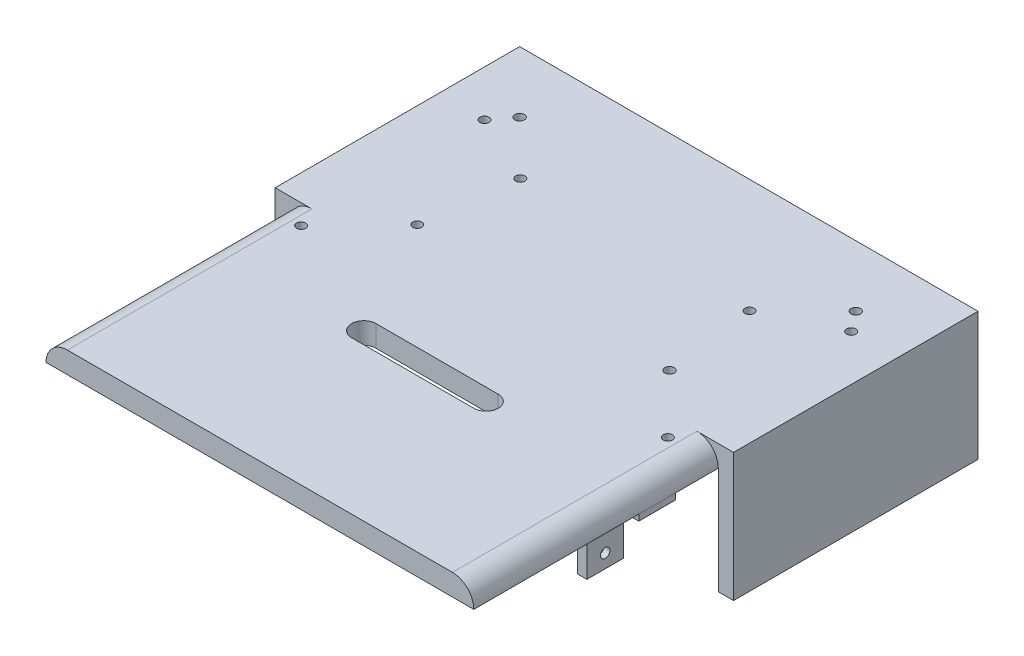
SolidWorks part; units mm, degrees
ref_plane "Front Plane" through (0, 0, 0) normal (0, 0, 1) x (1, 0, 0)
ref_plane "Top Plane" through (0, 0, 0) normal (0, 1, 0) x (1, 0, 0)
ref_plane "Right Plane" through (0, 0, 0) normal (1, 0, 0) x (0, 0, -1)
sketch "Sketch1" plane through (0, 0, 0) normal (0, 0, 1) x (1, 0, 0)
  line L0 (-95.0617, -14.5514) -> (-95.0617, 27.4486)
  line L1 (-95.0617, 27.4486) -> (54.9383, 27.4486)
  line L2 (54.9383, 27.4486) -> (54.9383, -14.5514)
  line L3 (54.9383, -14.5514) -> (49.9383, -14.5514)
  line L4 (49.9383, -14.5514) -> (49.9383, 20.4486)
  line L5 (49.9383, 20.4486) -> (-90.0617, 20.4486)
  line L6 (-90.0617, 20.4486) -> (-90.0617, -14.5514)
  line L7 (-90.0617, -14.5514) -> (-95.0617, -14.5514)
  dimension "D1" = 150
  dimension "D2" = 5
  dimension "D3" = 5
  dimension "D4" = 42
  dimension "D5" = 42
  dimension "D6" = 35
  dimension "D7" = 35
  dimension "D8" = 7
extrude "Boss-Extrude1" add sketch "Sketch1" along normal blind 160
sketch "Sketch2" plane through (0, 0, 0) normal (0, 0, -1) x (-1, 0, 0)
  line L0 (-52.4383, 15.4486) -> (-52.4383, -4.5514) construction
  line L1 (-50.9383, 15.4486) -> (-50.9383, -4.5514)
  line L2 (-53.9383, 15.4486) -> (-53.9383, -4.5514)
  line L3 (-4.9383, 23.9486) -> (45.0617, 23.9486) construction
  line L4 (-4.9383, 25.4486) -> (45.0617, 25.4486)
  line L5 (-4.9383, 22.4486) -> (45.0617, 22.4486)
  line L6 (92.5617, 15.4486) -> (92.5617, -4.5514) construction
  line L7 (94.0617, 15.4486) -> (94.0617, -4.5514)
  line L8 (91.0617, 15.4486) -> (91.0617, -4.5514)
  line L9 (-54.9383, 27.4486) -> (95.0617, 27.4486) construction
  line L12 (90.0617, 20.4486) -> (-49.9383, 20.4486) construction
  line L13 (-54.9383, -14.5514) -> (-54.9383, 27.4486) construction
  line L14 (-49.9383, 20.4486) -> (-49.9383, -14.5514) construction
  line L15 (90.0617, -14.5514) -> (90.0617, 20.4486) construction
  arc A0 (-50.9383, 15.4486) -> (-53.9383, 15.4486) centre (-52.4383, 15.4486) ccw
  arc A1 (-53.9383, -4.5514) -> (-50.9383, -4.5514) centre (-52.4383, -4.5514) ccw
  arc A2 (-4.9383, 25.4486) -> (-4.9383, 22.4486) centre (-4.9383, 23.9486) ccw
  arc A3 (45.0617, 22.4486) -> (45.0617, 25.4486) centre (45.0617, 23.9486) ccw
  arc A4 (94.0617, 15.4486) -> (91.0617, 15.4486) centre (92.5617, 15.4486) ccw
  arc A5 (91.0617, -4.5514) -> (94.0617, -4.5514) centre (92.5617, -4.5514) ccw
  point P2 (-52.4383, 5.4486)
  point P7 (20.0617, 23.9486)
  point P14 (92.5617, 5.4486)
  dimension "D1" = 22
  dimension "D2" = 3
  dimension "D3" = 20
  dimension "D4" = 2.5
  dimension "D5" = 3
  dimension "D6" = 20
  dimension "D7" = 2.5
  dimension "D8" = 22
  dimension "D9" = 3.5
  dimension "D10" = 3
  dimension "D11" = 50
  dimension "D12" = 75
extrude "Cut-Extrude1" cut sketch "Sketch2" against normal blind 32
sketch "Sketch3" plane through (-95.0617, 0, 0) normal (-1, 0, 0) x (0, 0, 1)
  line L0 (0, 27.4486) -> (0, -14.5514) construction
  line L3 (160, 27.4486) -> (0, 27.4486) construction
  circle A0 centre (120, 7.4486) radius 7.5
  dimension "D1" = 15
  dimension "D3" = 20
  dimension "D2" = 120
extrude "Cut-Extrude2" cut sketch "Sketch3" against normal blind 210
sketch "Sketch5" plane through (0, 27.4486, 0) normal (0, 1, 0) x (1, 0, 0)
  line L0 (54.9383, 0) -> (-95.0617, 0) construction
  line L1 (-95.0617, -160) -> (-95.0617, 0) construction
  line L2 (54.9383, -160) -> (54.9383, 0) construction
  circle A0 centre (-80.0617, -26.5) radius 1.5
  circle A1 centre (39.9383, -26.5) radius 1.5
  circle A2 centre (-80.0617, -86.5) radius 1.5
  circle A3 centre (39.9383, -86.5) radius 1.5
  dimension "D1" = 3
  dimension "D2" = 3
  dimension "D7" = 3
  dimension "D8" = 3
  dimension "D3" = 26.5
  dimension "D4" = 15
  dimension "D5" = 15
  dimension "D6" = 26.5
  dimension "D9" = 60
  dimension "D10" = 60
  dimension "D11" = 15
  dimension "D12" = 15
extrude "Cut-Extrude4" cut sketch "Sketch5" against normal blind 210
sketch "Sketch7" plane through (0, 27.4486, 0) normal (0, 1, 0) x (1, 0, 0)
  line L0 (-40.0617, -106) -> (-0.0617, -106) construction
  line L1 (-40.0617, -102) -> (-0.0617, -102)
  line L2 (-40.0617, -110) -> (-0.0617, -110)
  line L3 (-95.0617, -160) -> (-95.0617, 0) construction
  line L4 (54.9383, -160) -> (-95.0617, -160) construction
  arc A0 (-40.0617, -102) -> (-40.0617, -110) centre (-40.0617, -106) ccw
  arc A1 (-0.0617, -110) -> (-0.0617, -102) centre (-0.0617, -106) ccw
  point P2 (-20.0617, -106)
  dimension "D1" = 40
  dimension "D2" = 75
  dimension "D3" = 8
  dimension "D4" = 50
extrude "Cut-Extrude6" cut sketch "Sketch7" against normal blind 20
ref_plane "Plane5" through (-20.0617, 0, 0) normal (-1, 0, 0) x (0, 0, 1)
sketch "Sketch8" plane through (0, 27.4486, 0) normal (0, 1, 0) x (1, 0, 0)
  line L0 (54.9383, 0) -> (-95.0617, 0) construction
  line L1 (54.9383, -160) -> (54.9383, 0) construction
  line L2 (-95.0617, -160) -> (-95.0617, 0) construction
  circle A0 centre (-75.0617, -20) radius 1.55
  circle A1 centre (34.9383, -20) radius 1.55
  dimension "D1" = 3.1
  dimension "D2" = 3.1
  dimension "D3" = 20
  dimension "D4" = 20
  dimension "D5" = 20
  dimension "D6" = 20
extrude "Cut-Extrude7" cut sketch "Sketch8" against normal blind 10
sketch "Sketch9" plane through (0, 20.4486, 0) normal (0, -1, 0) x (1, 0, 0)
  line L0 (49.9383, 106) -> (29.9383, 106)
  line L1 (49.9383, 160) -> (49.9383, 0) construction
  line L2 (29.9383, 106) -> (29.9383, 94)
  line L3 (29.9383, 94) -> (49.9383, 94)
  line L4 (49.9383, 94) -> (49.9383, 106)
  line L5 (-90.0617, 160) -> (49.9383, 160) construction
  dimension "D1" = 20
  dimension "D2" = 12
  dimension "D3" = 54
extrude "Boss-Extrude3" add sketch "Sketch9" along normal blind 2
sketch "Sketch10" plane through (0, 18.4486, 0) normal (0, -1, 0) x (1, 0, 0)
  line L0 (29.9383, 106) -> (32.9383, 106)
  line L1 (49.9383, 106) -> (29.9383, 106) construction
  line L2 (32.9383, 106) -> (32.9383, 94)
  line L3 (29.9383, 94) -> (49.9383, 94) construction
  line L4 (32.9383, 94) -> (29.9383, 94)
  line L5 (29.9383, 94) -> (29.9383, 106)
  dimension "D1" = 3
extrude "Boss-Extrude4" add sketch "Sketch10" along normal blind 25
sketch "Sketch11" plane through (29.9383, 0, 0) normal (-1, 0, 0) x (0, 0, 1)
  line L0 (106, -6.5514) -> (94, -6.5514) construction
  line L1 (106, -6.5514) -> (106, 20.4486) construction
  circle A0 centre (100, 15.9486) radius 3.5
  circle A1 centre (100, -2.0514) radius 3.5
  dimension "D1" = 7
  dimension "D2" = 7
  dimension "D4" = 4.5
  dimension "D3" = 18
  dimension "D5" = 6
  dimension "D6" = 6
extrude "Cut-Extrude8" cut sketch "Sketch11" against normal blind 1
sketch "Sketch12" plane through (30.9383, 0, 0) normal (-1, 0, 0) x (0, 0, 1)
  circle A0 centre (100, 15.9486) radius 1.55
  circle A1 centre (100, -2.0514) radius 1.55
  dimension "D1" = 3.1
  dimension "D2" = 3.1
extrude "Cut-Extrude9" cut sketch "Sketch12" against normal blind 3
mirror "Mirror1" about plane through (-20.0617, 0, 0) normal (-1, 0, 0) of "Cut-Extrude8", "Boss-Extrude4", "Boss-Extrude3", "Cut-Extrude9"
sketch "Sketch13" plane through (0, 27.4486, 0) normal (0, 1, 0) x (1, 0, 0)
  line L0 (-95.0617, -160) -> (-95.0617, 0) construction
  line L1 (54.9383, -160) -> (54.9383, 0) construction
  circle A0 centre (17.4383, -37.2658) radius 1.5
  circle A1 centre (-57.5617, -37.2658) radius 1.5
  circle A2 centre (-61.3417, -67.2238) radius 1.5
  circle A3 centre (21.2183, -67.2238) radius 1.55
  dimension "D1" = 3
  dimension "D2" = 3
  dimension "D3" = 3
  dimension "D4" = 3.1
  dimension "D5" = 75
  dimension "D6" = 37.5
  dimension "D7" = 37.5
  dimension "D8" = 82.56
  dimension "D9" = 33.72
  dimension "D10" = 33.72
extrude "Cut-Extrude10" cut sketch "Sketch13" against normal blind 10
sketch "Sketch14" plane through (0, 20.4486, 0) normal (0, -1, 0) x (1, 0, 0)
  line L0 (2.1394, 81.6504) -> (2.1394, 56.6504) construction
  line L1 (5.1394, 81.6504) -> (5.1394, 56.6504)
  line L2 (-0.8606, 81.6504) -> (-0.8606, 56.6504)
  line L3 (-39.8606, 81.6504) -> (-39.8606, 56.6504) construction
  line L4 (-36.8606, 81.6504) -> (-36.8606, 56.6504)
  line L5 (-42.8606, 81.6504) -> (-42.8606, 56.6504)
  arc A0 (5.1394, 81.6504) -> (-0.8606, 81.6504) centre (2.1394, 81.6504) ccw
  arc A1 (-0.8606, 56.6504) -> (5.1394, 56.6504) centre (2.1394, 56.6504) ccw
  arc A2 (-36.8606, 81.6504) -> (-42.8606, 81.6504) centre (-39.8606, 81.6504) ccw
  arc A3 (-42.8606, 56.6504) -> (-36.8606, 56.6504) centre (-39.8606, 56.6504) ccw
  circle A4 centre (2.1394, 69.1504) radius 1.375
  circle A6 centre (-39.8606, 69.1504) radius 1.375
  point P2 (2.1394, 69.1504)
  point P7 (-39.8606, 69.1504)
  dimension "D5" = 2.75
  dimension "D6" = 2.75
  dimension "D1" = 6
  dimension "D2" = 6
  dimension "D3" = 25
  dimension "D4" = 25
  dimension "D7" = 42
extrude "Boss-Extrude5" add sketch "Sketch14" along normal blind 5
sketch "Sketch15" plane through (54.9383, 0, 0) normal (1, 0, 0) x (0, 0, -1)
  line L0 (-160, 27.4486) -> (-80, 27.4486)
  line L1 (-160, 27.4486) -> (0, 27.4486) construction
  line L2 (-80, 27.4486) -> (-80, -14.5514)
  line L3 (-160, -14.5514) -> (0, -14.5514) construction
  line L4 (-80, -14.5514) -> (-160, -14.5514)
  line L5 (-160, -14.5514) -> (-160, 27.4486)
extrude "Cut-Extrude11" cut sketch "Sketch15" against normal blind 5
fillet "Fillet1" radius 7 1 edges at (49.9383, 27.4486, 120)
sketch "Sketch16" plane through (-95.0617, 0, 0) normal (-1, 0, 0) x (0, 0, 1)
  line L0 (160, 27.4486) -> (80, 27.4486)
  line L1 (80, 27.4486) -> (80, -14.5514)
  line L2 (160, -14.5514) -> (0, -14.5514) construction
  line L3 (80, -14.5514) -> (160, -14.5514)
  line L4 (160, -14.5514) -> (160, 27.4486)
extrude "Cut-Extrude12" cut sketch "Sketch16" against normal blind 5
fillet "Fillet2" radius 7 1 edges at (-90.0617, 27.4486, 120)
